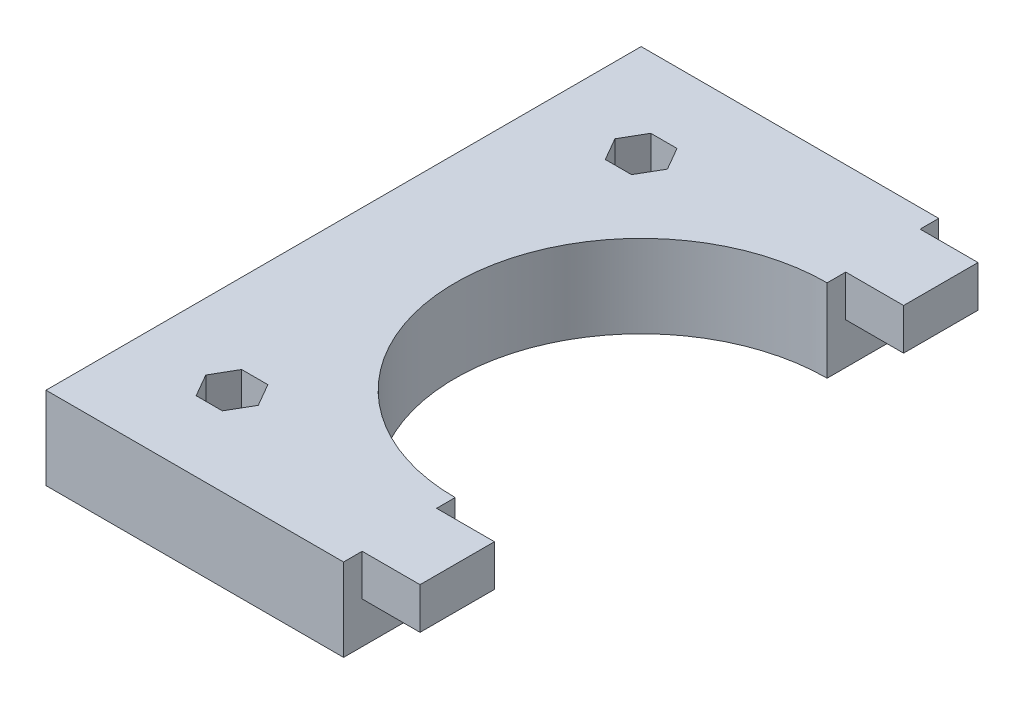
SolidWorks part; units mm, degrees
ref_plane "Front Plane" through (0, 0, 0) normal (0, 0, 1) x (1, 0, 0)
ref_plane "Top Plane" through (0, 0, 0) normal (0, 1, 0) x (1, 0, 0)
ref_plane "Right Plane" through (0, 0, 0) normal (1, 0, 0) x (0, 0, -1)
sketch "Sketch1" plane through (0, 0, 0) normal (0, 1, 0) x (1, 0, 0)
  line L0 (0, 74.1448) -> (0, -72.8187)
  line L1 (-36, -36) -> (36, -36)
  line L2 (-36, -36) -> (-36, 36)
  line L3 (-36, 36) -> (36, 36)
  line L4 (36, -36) -> (36, 36)
  line L5 (-36, -36) -> (36, 36) construction
  line L6 (-36, 36) -> (36, -36) construction
  circle A0 centre (0, 0) radius 22.5
  circle A1 centre (-24.7487, 24.7487) radius 1.5
  circle A2 centre (24.7487, 24.7487) radius 1.5
  circle A3 centre (24.7487, -24.7487) radius 1.5
  circle A4 centre (-24.7487, -24.7487) radius 1.5
  point P0 (0, 0)
  point P21 (0, 0)
  dimension "D1" = 45
  dimension "D5" = 3
  dimension "D2" = 36
  dimension "D3" = 36
  dimension "D4" = 0
  dimension "D7" = 35
  dimension "D8" = 0
  dimension "D6" = 4
extrude "Boss-Extrude1" add sketch "Sketch1" along normal blind 5 and the other way blind 5 contours A0 L0 L3 L2 L1 region at (-0.805, 0, -29.25)
sketch "Sketch2" plane through (0, 5, 0) normal (0, 1, 0) x (1, 0, 0)
  line L0 (-36, 36) -> (0, 36) construction
  line L1 (-23.161, 27.4987) -> (-26.3365, 27.4987)
  line L2 (-26.3365, 27.4987) -> (-27.9242, 24.7487)
  line L3 (-27.9242, 24.7487) -> (-26.3365, 21.9987)
  line L4 (-26.3365, 21.9987) -> (-23.161, 21.9987)
  line L5 (-23.161, 21.9987) -> (-21.5733, 24.7487)
  line L6 (-21.5733, 24.7487) -> (-23.161, 27.4987)
  circle A0 centre (-24.7487, 24.7487) radius 2.75 construction
  dimension "D1" = 5.5
  dimension "D2" = 0
extrude "Cut-Extrude1" cut sketch "Sketch2" against normal blind 5
mirror "Mirror1" about plane through (0, 0, 0) normal (0, 0, 1) of "Cut-Extrude1"
sketch "Sketch3" plane through (0, 5, 0) normal (0, 1, 0) x (1, 0, 0)
  line L0 (0, -22.5) -> (0, -36) construction
  line L1 (0, -24.75) -> (7, -24.75)
  line L2 (0, -24.75) -> (0, -33.75)
  line L3 (0, -33.75) -> (7, -33.75)
  line L4 (7, -24.75) -> (7, -33.75)
  line L5 (-36, -36) -> (0, -36) construction
  dimension "D1" = 9
  dimension "D2" = 2.25
  dimension "D3" = 7
extrude "Boss-Extrude2" add sketch "Sketch3" against normal blind 5
sketch "Sketch4" plane through (0, -5, 0) normal (0, -1, 0) x (1, 0, 0)
  line L0 (0, -36) -> (0, -22.5) construction
  line L1 (0, -24.625) -> (-9.4543, -24.625)
  line L2 (0, -24.625) -> (0, -33.875)
  line L3 (0, -33.875) -> (-9.4543, -33.875)
  line L4 (-9.4543, -24.625) -> (-9.4543, -33.875)
  line L5 (-36, -36) -> (0, -36) construction
  dimension "D1" = 9.25
  dimension "D2" = 2.125
extrude "Cut-Extrude2" [suppressed] cut sketch "Sketch4" against normal blind 5
mirror "Mirror2" about plane through (0, 0, 0) normal (0, 0, 1) of "Boss-Extrude2"
